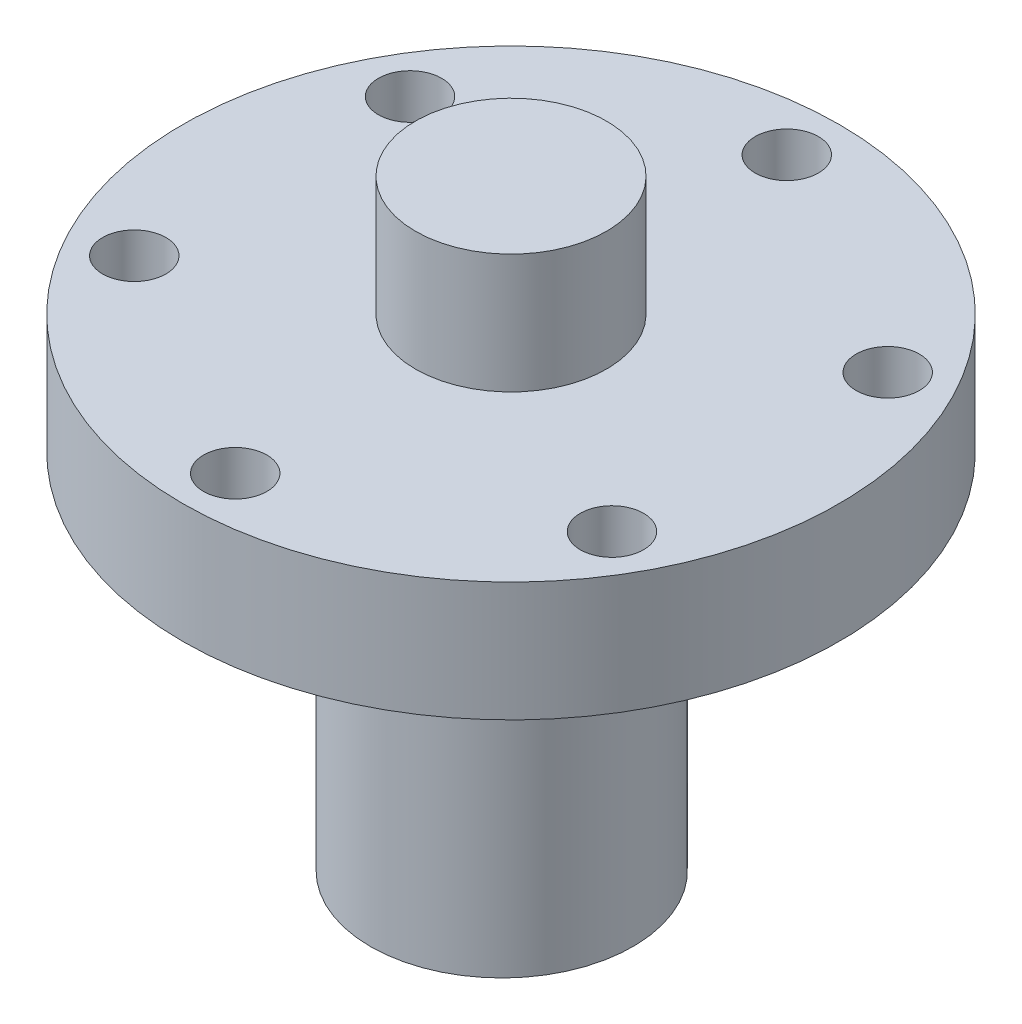
SolidWorks part; units mm, degrees
ref_plane "Front Plane" through (0, 0, 0) normal (0, 0, 1) x (1, 0, 0)
ref_plane "Top Plane" through (0, 0, 0) normal (0, 1, 0) x (1, 0, 0)
ref_plane "Right Plane" through (0, 0, 0) normal (1, 0, 0) x (0, 0, -1)
sketch "Sketch1" plane through (0, 0, 0) normal (0, 1, 0) x (1, 0, 0)
  circle A0 centre (0, 0) radius 34.925
  dimension "D1" = 69.85
extrude "Extrude1" add sketch "Sketch1" along normal blind 12.7
sketch "Sketch2" plane through (0, 0, 0) normal (0, 1, 0) x (1, 0, 0)
  circle A0 centre (0, 0) radius 17.399
  dimension "D1" = 34.798
extrude "Cut-Extrude1" [suppressed] cut sketch "Sketch2" along normal through all
sketch "Sketch3" plane through (0, 0, 0) normal (0, 1, 0) x (1, 0, 0)
  circle A0 centre (0, 29.337) radius 3.3655
  dimension "D1" = 6.731
  dimension "D2" = 29.337
extrude "Cut-Extrude2" cut sketch "Sketch3" along normal blind 12.7
ref_axis "Axis1" through (0, 35.8582, 0) along (0, -1, 0)
pattern_circular "CirPattern1" count 6 over 360 about axis through (0, 35.8582, 0) along (0, -1, 0) of "Cut-Extrude2"
sketch "Sketch4" plane through (0, 0, 0) normal (0, 1, 0) x (1, 0, 0)
  line L0 (0, 0) -> (0, 16.8619)
ref_plane "Plane1" through (0, 12.7, 0) normal (0, 1, 0) x (-1, 0, 0)
sketch "Sketch6" plane through (0, 12.7, 0) normal (0, 1, 0) x (-1, 0, 0)
  circle A0 centre (0, 0) radius 10.16
  dimension "D1" = 20.32
extrude "Extrude2" add sketch "Sketch6" along normal blind 12.7
ref_plane "Plane2" through (0, 0, 0) normal (0, -1, 0) x (1, 0, 0)
sketch "Sketch7" plane through (0, 0, 0) normal (0, -1, 0) x (1, 0, 0)
  circle A0 centre (0, 0.9829) radius 12.7
  dimension "D1" = 25.4
extrude "Extrude-Thin2" add sketch "Sketch7" along normal blind 38.1 thin thin type one direction wall 1.27
sketch "Sketch8" plane through (0, 0, 0) normal (0, -1, 0) x (1, 0, 0)
  circle A0 centre (0, 0) radius 2.54
extrude "Extrude4" add sketch "Sketch8" along normal blind 38.1
